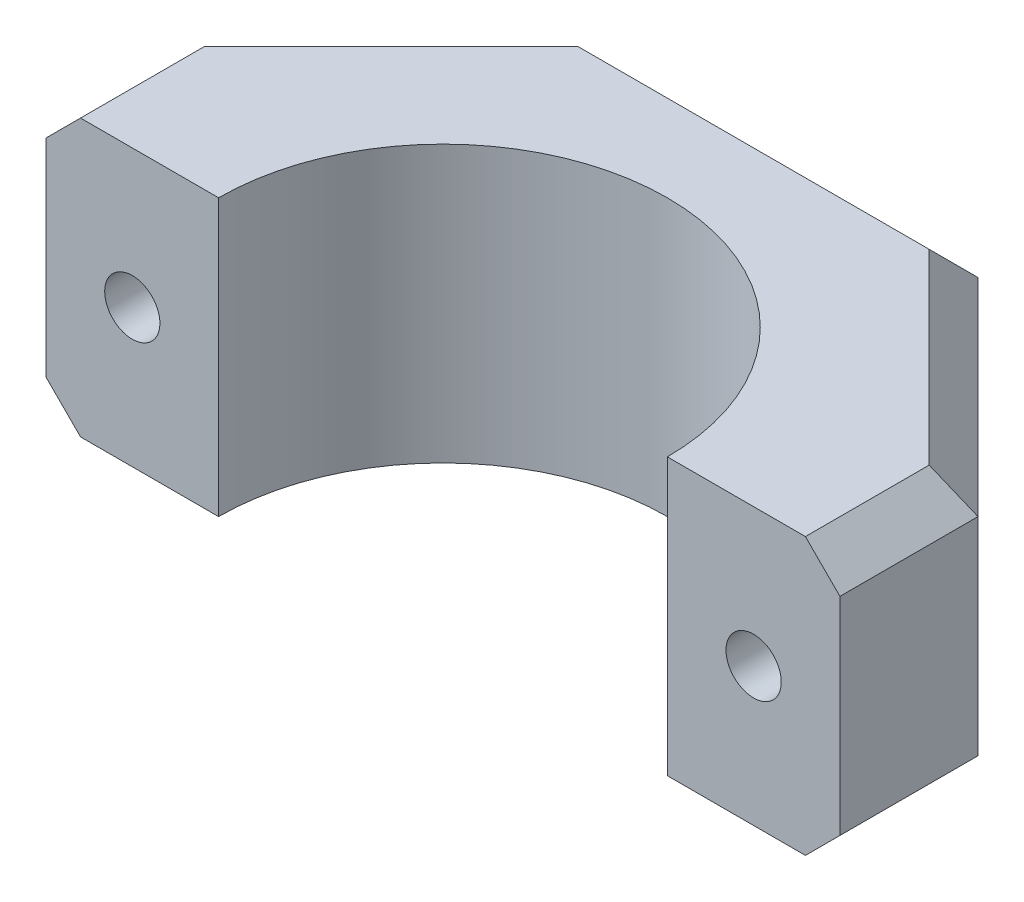
SolidWorks part; units mm, degrees
ref_plane "Front Plane" through (0, 0, 0) normal (0, 0, 1) x (1, 0, 0)
ref_plane "Top Plane" through (0, 0, 0) normal (0, 1, 0) x (1, 0, 0)
ref_plane "Right Plane" through (0, 0, 0) normal (1, 0, 0) x (0, 0, -1)
sketch "Sketch1" plane through (0, 0, 0) normal (0, 1, 0) x (1, 0, 0)
  line L0 (-34.4855, -2.0289) -> (-44.4855, -2.0289)
  line L1 (-44.4855, -2.0289) -> (-44.4855, 17.9711)
  line L2 (-44.4855, 17.9711) -> (1.5145, 17.9711)
  line L3 (1.5145, 17.9711) -> (1.5145, -2.0289)
  line L4 (1.5145, -2.0289) -> (-8.4855, -2.0289)
  arc A0 (-34.4855, -2.0289) -> (-8.4855, -2.0289) centre (-21.4855, -2.0289) cw
  dimension "D1" = 13
  dimension "D2" = 10
  dimension "D3" = 20
extrude "Boss-Extrude1" add sketch "Sketch1" along normal blind 16
chamfer "Chamfer1" distance 12 distance2 12 2 edges at (1.5145, 8, -17.9711) (-44.4855, 8, -17.9711)
sketch "Sketch2" plane through (0, 0, -17.9711) normal (0, 0, -1) x (-1, 0, 0)
  line L0 (44.4855, 16) -> (44.4855, 0) construction
  line L1 (-1.5145, 16) -> (-1.5145, 0) construction
  line L2 (10.4855, 0) -> (32.4855, 0) construction
  circle A0 centre (3.4855, 8) radius 1.6
  circle A1 centre (39.4855, 8) radius 1.6
  circle A2 centre (39.4855, 8) radius 3
  circle A3 centre (3.4855, 8) radius 3
  point P8 (-1.5145, 8)
  dimension "D4" = 3.2
  dimension "D5" = 6
  dimension "D1" = 5
  dimension "D2" = 5
  dimension "D3" = 8
extrude "Cut-Extrude1" cut sketch "Sketch2" against normal up to surface (20 mm away) contours A1 | A0 region at (-3.4855, 8, -17.9711) region at (-39.4855, 8, -17.9711) up to face at (-39.4855, 8, 2.0289)
extrude "Cut-Extrude2" cut sketch "Sketch2<4>" against normal offset from surface (16 mm away) 4 up to face at (-41.0855, 8, 2.0289)
sketch "Sketch2<4>" plane through (0, 0, -17.9711) normal (0, 0, -1) x (-1, 0, 0) same geometry as "Sketch2"
chamfer "Chamfer2" distance 2 angle 45 10 edges at (-44.4855, 0, -1.9711) (-38.4855, 0, -11.9711) (1.5145, 0, -1.9711) (-21.4855, 0, -17.9711) (-4.4855, 0, -11.9711) (1.5145, 16, -1.9711) (-44.4855, 16, -1.9711) (-38.4855, 16, -11.9711) (-21.4855, 16, -17.9711) (-4.4855, 16, -11.9711)
